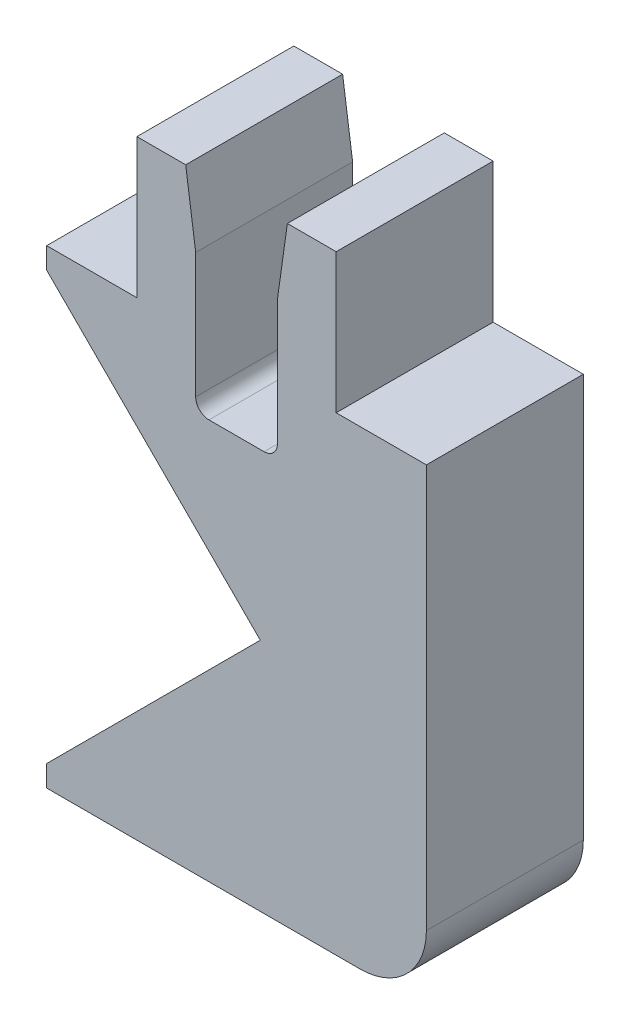
SolidWorks part; units mm, degrees
note: '?' marks a value the reader was unsure of.
material "Acrylic (Medium-high impact)"
ref_plane "Front Plane" through (0, 0, 0) normal (0, 0, 1) x (1, 0, 0)
ref_plane "Top Plane" through (0, 0, 0) normal (0, 1, 0) x (1, 0, 0)
ref_plane "Right Plane" through (0, 0, 0) normal (1, 0, 0) x (0, 0, -1)
sketch "Sketch1" plane through (0, 0, 0) normal (0, 0, 1) x (1, 0, 0)
  line L0 (0, 0) -> (-8.1675, 8.1675)
  line L1 (-8.1675, 8.1675) -> (-8.1675, 8.9803)
  line L2 (-8.1675, 8.9803) -> (-4.7187, 8.9803)
  line L3 (-4.7187, 8.9803) -> (-4.7187, 14.3143)
  line L4 (-4.7187, 14.3143) -> (2.9013, 14.3143)
  line L5 (2.9013, 14.3143) -> (2.9013, 8.9803)
  line L6 (2.9013, 8.9803) -> (6.35, 8.9803)
  line L7 (6.35, 8.9803) -> (6.35, -8.9803)
  line L8 (6.35, -8.9803) -> (-8.1675, -8.9803)
  line L9 (-8.1675, -8.9803) -> (-8.1675, -8.1675)
  line L10 (-8.1675, -8.1675) -> (0, 0)
  line L11 (0, 0) -> (-8.9803, 8.9803) construction
  dimension "D1" = 45
  dimension "D2" = 12.7
  dimension "D3" = 0.8128
  dimension "D4" = 6.35
  dimension "D5" = 5.334
  dimension "D6" = 7.62
extrude "Boss-Extrude1" add sketch "Sketch1" along normal blind 6
fillet "Fillet1" radius 2.54 1 edges at (6.35, -8.9803, 3)
sketch "Sketch2" plane through (0, 0, 6) normal (0, 0, 1) x (1, 0, 0)
  line L0 (2.9013, 14.3143) -> (-4.7187, 14.3143) construction
  line L1 (-2.4708, 14.3143) -> (0.6534, 14.3143)
  line L2 (-2.4708, 14.3143) -> (-2.4708, 6.3133)
  line L3 (-2.4708, 6.3133) -> (0.6534, 6.3133)
  line L4 (0.6534, 14.3143) -> (0.6534, 6.3133)
  line L5 (-0.9087, 6.3133) -> (-0.9087, 14.3143) construction
  line L6 (-8.3355, 14.5683) -> (7.3282, 14.5683) construction
  line L7 (6.35, 8.9803) -> (2.9013, 8.9803) construction
  dimension "D1" = 3.1242
  dimension "D2" = 8.001
  dimension "D3" = 5.588
extrude "Cut-Extrude1" cut sketch "Sketch2" against normal through all
chamfer "Chamfer1" distance 0.381 angle 82 2 edges at (0.6534, 14.3143, 3) (-2.4708, 14.3143, 3)
fillet "Fillet2" radius 0.508 2 edges at (0.6534, 6.3133, 3) (-2.4708, 6.3133, 3)
ref_point "Point1"
ref_axis "Axis1" through (-0.9087, 6.3133, 3) along (0, 1, 0)?
